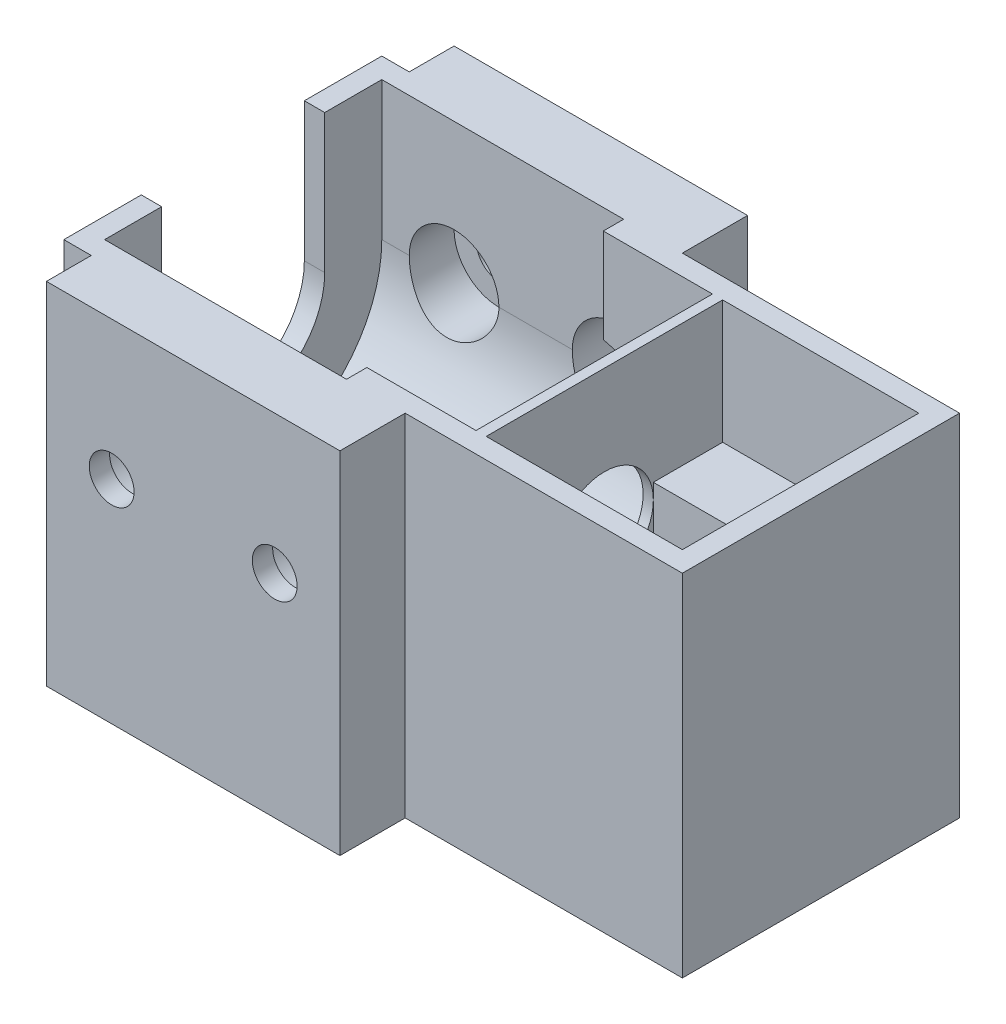
SolidWorks part; units mm, degrees
ref_plane "Front Plane" through (0, 0, 0) normal (0, 0, 1) x (1, 0, 0)
ref_plane "Top Plane" through (0, 0, 0) normal (0, 1, 0) x (1, 0, 0)
ref_plane "Right Plane" through (0, 0, 0) normal (1, 0, 0) x (0, 0, -1)
sketch "Sketch1" plane through (0, 0, 0) normal (0, 0, 1) x (1, 0, 0)
  line L1 (-76.2, -50.8) -> (40.64, -50.8)
  line L2 (-76.2, -50.8) -> (-76.2, 0)
  line L3 (-76.2, 0) -> (40.64, 0)
  line L4 (40.64, -50.8) -> (40.64, 0)
  line L5 (-76.2, -50.8) -> (40.64, 0) construction
  line L6 (-76.2, 0) -> (40.64, -50.8) construction
  point P0 (0, 0)
  dimension "D1" = 116.84
  dimension "D2" = 50.8
  dimension "D3" = 76.2
extrude "Boss-Extrude1" add sketch "Sketch1" along normal mid plane 63.5
sketch "Sketch2" plane through (0, 0, 0) normal (0, 0, 1) x (1, 0, 0)
  line L0 (-152.4829, -25.4) -> (6, -25.4) construction
  line L1 (-49.3609, -3.81) -> (-49.3609, -12.7)
  line L2 (40.64, 0) -> (-76.2, 0) construction
  line L3 (40.64, 0) -> (-76.2, 0) construction
  line L4 (-11.68, -3.81) -> (-11.68, -6.985)
  line L5 (-11.68, -25.4) -> (-11.68, -3.81) construction
  line L6 (-128.4172, -25.4) -> (-157.8092, -25.4)
  line L7 (6, -25.4) -> (40.64, -25.4)
  line L8 (-607.3619, -25.4) -> (6, -25.4) construction
  line L9 (-49.3609, -3.81) -> (-11.68, -3.81)
  line L10 (6, -25.4) -> (-128.4172, -25.4)
  line L11 (-11.68, -6.985) -> (5.32, -6.985)
  line L12 (5.32, -6.985) -> (5.32, -17.78)
  line L13 (5.32, -17.78) -> (23.32, -17.78)
  line L14 (-49.3609, -12.7) -> (-220.2024, -12.7)
  line L15 (-220.2024, -12.7) -> (-220.2024, -25.4)
  line L16 (-220.2024, -25.4) -> (-157.8092, -25.4)
  line L17 (23.32, -17.78) -> (23.32, -25.4) construction
  line L18 (23.32, -17.78) -> (40.64, -17.78)
  line L19 (40.64, -50.8) -> (40.64, 0) construction
  line L20 (40.64, -17.78) -> (40.64, -25.4)
  line L21 (-76.2, 0) -> (-76.2, -50.8) construction
  point P23 (-11.68, -25.4)
  dimension "D1" = 21.59
  dimension "D2" = 37.6809
  dimension "D3" = 25.4
  dimension "D4" = 35
  dimension "D5" = 7.62
  dimension "D6" = 3.175
  dimension "D7" = 26.8391
  dimension "D8" = 18
  dimension "D9" = 12.7
revolve "Cut-Revolve1" cut sketch "Sketch2" angle 360 about L0
sketch "Sketch38" plane through (40.64, 0, 0) normal (1, 0, 0) x (0, 0, -1)
  line L1 (-10, -35.4) -> (10, -35.4)
  line L2 (-10, -35.4) -> (-10, -15.4)
  line L3 (-10, -15.4) -> (10, -15.4)
  line L4 (10, -35.4) -> (10, -15.4)
  line L5 (-10, -35.4) -> (10, -15.4) construction
  line L6 (-10, -15.4) -> (10, -35.4) construction
  point P0 (0, -25.4)
  point P1 (0, -25.4)
  dimension "D1" = 20
  dimension "D2" = 20
extrude "Cut-Extrude33" cut sketch "Sketch38" against normal offset from surface (33.7325 mm away) 1.5875 up to face at (5.32, -43.815, 0)
sketch "Sketch37" plane through (40.64, 0, 0) normal (1, 0, 0) x (0, 0, -1)
  line L0 (31.75, -50.8) -> (31.75, 0) construction
  line L1 (-31.75, 0) -> (31.75, 0)
  line L2 (-31.75, 0) -> (-31.75, -25.4)
  line L3 (-31.75, -25.4) -> (31.75, -25.4)
  line L4 (31.75, 0) -> (31.75, -25.4)
  line L5 (10, -35.4) -> (10, -15.4) construction
  point P7 (0, -25.4)
  point P11 (0, 0)
  point P14 (10, -25.4)
extrude "Cut-Extrude32" cut sketch "Sketch37" against normal through all
sketch "Sketch39" plane through (0, -25.4, 0) normal (0, 1, 0) x (1, 0, 0)
  line L10 (-76.2, 12.7) -> (-49.3609, 12.7)
  line L11 (-49.3609, 12.7) -> (-49.3609, 21.59)
  line L12 (-49.3609, 21.59) -> (-11.68, 21.59)
  line L13 (-11.68, 21.59) -> (-11.68, 18.415)
  line L14 (-11.68, 18.415) -> (5.32, 18.415)
  line L15 (5.32, 18.415) -> (5.32, 7.62)
  line L16 (5.32, 18.415) -> (5.32, 7.62)
  line L17 (40.64, 10) -> (40.64, 31.75)
  line L18 (40.64, 31.75) -> (-76.2, 31.75)
  line L19 (-76.2, 31.75) -> (-76.2, 12.7)
  line L20 (-76.2, 12.7) -> (-49.3609, 12.7)
  line L21 (-49.3609, 12.7) -> (-49.3609, 21.59)
  line L22 (-49.3609, 21.59) -> (-11.68, 21.59)
  line L23 (-11.68, 21.59) -> (-11.68, 18.415)
  line L24 (-11.68, 18.415) -> (5.32, 18.415)
  line L25 (6.9075, 10) -> (40.64, 10)
  line L26 (6.9075, 10) -> (40.64, 10)
  line L27 (40.64, 10) -> (40.64, 31.75)
  line L28 (40.64, 31.75) -> (-76.2, 31.75)
  line L29 (-76.2, 31.75) -> (-76.2, 12.7)
  line L30 (-49.3609, -12.7) -> (-76.2, -12.7)
  line L31 (-76.2, -12.7) -> (-76.2, -31.75)
  line L32 (-76.2, -31.75) -> (40.64, -31.75)
  line L33 (40.64, -31.75) -> (40.64, -10)
  line L34 (40.64, -10) -> (6.9075, -10)
  line L35 (40.64, -10) -> (6.9075, -10)
  line L36 (5.32, -18.415) -> (-11.68, -18.415)
  line L37 (-11.68, -18.415) -> (-11.68, -21.59)
  line L38 (-11.68, -21.59) -> (-49.3609, -21.59)
  line L39 (-49.3609, -21.59) -> (-49.3609, -12.7)
  line L40 (-49.3609, -12.7) -> (-76.2, -12.7)
  line L41 (-76.2, -12.7) -> (-76.2, -31.75)
  line L42 (-76.2, -31.75) -> (40.64, -31.75)
  line L43 (40.64, -31.75) -> (40.64, -10)
  line L44 (5.32, -7.62) -> (5.32, -18.415)
  line L45 (5.32, -7.62) -> (5.32, -18.415)
  line L46 (5.32, -18.415) -> (-11.68, -18.415)
  line L47 (-11.68, -18.415) -> (-11.68, -21.59)
  line L48 (-11.68, -21.59) -> (-49.3609, -21.59)
  line L49 (-49.3609, -21.59) -> (-49.3609, -12.7)
  line L52 (5.32, 7.62) -> (6.9075, 7.62)
  line L53 (5.32, 7.62) -> (6.9075, 7.62)
  line L54 (6.9075, 7.62) -> (6.9075, 10)
  line L55 (6.9075, 7.62) -> (6.9075, 10)
  line L56 (6.9075, -10) -> (6.9075, -7.62)
  line L57 (6.9075, -10) -> (6.9075, -7.62)
  line L58 (6.9075, -7.62) -> (5.32, -7.62)
  line L59 (6.9075, -7.62) -> (5.32, -7.62)
  dimension "D1" = 0
  dimension "D2" = 0
extrude "Boss-Extrude5" add sketch "Sketch39" along normal blind 25.4
sketch "Sketch40" plane through (0, 0, 0) normal (0, 1, 0) x (1, 0, 0)
  line L0 (6.9075, 10) -> (40.64, 10) construction
  line L1 (23.32, 10) -> (40.64, 10)
  line L2 (23.32, 10) -> (23.32, -10)
  line L3 (23.32, -10) -> (40.64, -10)
  line L4 (40.64, 10) -> (40.64, -10)
  line L6 (-11.68, 21.59) -> (-11.68, 18.415) construction
  dimension "D1" = 35
extrude "Boss-Extrude6" add sketch "Sketch40" against normal up to next
sketch "Sketch41" plane through (0, 0, 0) normal (0, 1, 0) x (1, 0, 0)
  line L2 (-76.2, 12.7) -> (-76.2, -12.7) construction
  circle A0 centre (-57.15, 0) radius 3.1134
  circle A1 centre (-31.75, 0) radius 3.1134
  circle A2 centre (-6.35, 0) radius 3.1134
  dimension "D1" = 19.05
extrude "Cut-Extrude34" cut sketch "Sketch41" against normal through all
ref_plane "Plane_Mid" through (0, -25.4, 0) normal (0, 1, 0) x (1, 0, 0)
ref_axis "Axis1" through (6.9075, -25.4, 0) along (-1, 0, 0)
sketch "Sketch42" plane through (0, 0, 0) normal (0, 0, 1) x (1, 0, 0)
  line L0 (1.7462, -25.4) -> (-1.7462, -25.4) construction
  line L1 (-76.2, 0) -> (-76.2, -25.4) construction
  circle A0 centre (-38.1, -25.4) radius 3.4925
  circle A1 centre (-12.7, -25.4) radius 3.4925
  dimension "D1" = 6.985
  dimension "D2" = 38.1
extrude "Cut-Extrude35" cut sketch "Sketch42" against normal through all both and the other way through all
sketch "Sketch43" plane through (0, 0, 0) normal (0, 0, 1) x (1, 0, 0)
  circle A0 centre (-38.1, -25.4) radius 6.985
  circle A1 centre (-12.7, -25.4) radius 6.985
  dimension "D1" = 13.97
extrude "Cut-Extrude36" cut sketch "Sketch43" against normal offset from surface (28.575 mm away) 3.175 up to face at (-9.2075, -25.4, -31.75)
extrude "Cut-Extrude37" cut sketch "Sketch43<2>" along normal offset from surface (28.575 mm away) 3.175 up to face at (-9.2075, -25.4, 31.75)
sketch "Sketch43<2>" plane through (0, 0, 0) normal (0, 0, 1) x (1, 0, 0) same geometry as "Sketch43"
sketch "Sketch44" plane through (0, 0, 0) normal (0, 1, 0) x (1, 0, 0)
  line L0 (5.32, -18.415) -> (-11.68, -18.415) construction
  line L1 (6.9075, 18.415) -> (22.82, 18.415)
  line L2 (6.9075, 18.415) -> (6.9075, -18.415)
  line L3 (6.9075, -18.415) -> (22.82, -18.415)
  line L4 (22.82, 18.415) -> (22.82, -18.415)
  line L5 (-11.68, 18.415) -> (5.32, 18.415) construction
  line L6 (6.9075, 7.62) -> (6.9075, 10) construction
  line L7 (23.32, 10) -> (23.32, -10) construction
  dimension "D1" = 0.5
extrude "Cut-Extrude38" cut sketch "Sketch44" against normal up to surface (35.4 mm away) up to face at (15.1138, -35.4, 0)
sketch "Sketch45" plane through (0, 0, 0) normal (0, 0, 1) x (1, 0, 0)
  line L0 (40.64, 0) -> (-76.2, 0) construction
  line L2 (37.465, 0) -> (22.82, 0)
  line L4 (37.465, 0) -> (37.465, -15.4)
  line L5 (37.465, -15.4) -> (22.82, -15.4)
  line L8 (22.82, 0) -> (22.82, -15.4)
  line L9 (40.64, -50.8) -> (40.64, 0) construction
  line L10 (22.82, -35.4) -> (22.82, 0) construction
  line L11 (-5.715, -25.4) -> (5.32, -25.4) construction
  dimension "D1" = 3.175
  dimension "D2" = 10
extrude "Cut-Extrude39" cut sketch "Sketch45" against normal up to surface and the other way up to surface up to face at (14.8637, -17.7, -18.415) other way up to face at (14.8638, -17.7, 18.415)
sketch "Sketch46" plane through (0, 0, 0) normal (0, 1, 0) x (1, 0, 0)
  line L0 (-11.68, 18.415) -> (5.32, 18.415) construction
  line L1 (40.64, 31.75) -> (-2.54, 31.75)
  line L2 (40.64, 31.75) -> (40.64, 21.59)
  line L3 (40.64, 21.59) -> (-2.54, 21.59)
  line L4 (-2.54, 31.75) -> (-2.54, 21.59)
  line L5 (-76.2, 0) -> (40.64, 0) construction
  line L6 (-76.2, 12.7) -> (-76.2, -12.7) construction
  line L7 (40.64, -31.75) -> (40.64, 31.75) construction
  line L8 (40.64, -31.75) -> (40.64, -21.59)
  line L9 (40.64, -21.59) -> (-2.54, -21.59)
  line L10 (40.64, -31.75) -> (-2.54, -31.75)
  line L11 (-2.54, -31.75) -> (-2.54, -21.59)
  line L12 (-49.3609, 21.59) -> (-11.68, 21.59) construction
  line L13 (-76.2, 31.75) -> (-48.26, 31.75)
  line L14 (-76.2, 31.75) -> (-76.2, 24.765)
  line L15 (-76.2, 24.765) -> (-48.26, 24.765)
  line L16 (-48.26, 31.75) -> (-48.26, 24.765)
  line L17 (-48.26, -31.75) -> (-48.26, -24.765)
  line L18 (-76.2, -24.765) -> (-48.26, -24.765)
  line L19 (-76.2, -31.75) -> (-76.2, -24.765)
  line L20 (-76.2, -31.75) -> (-48.26, -31.75)
  dimension "D1" = 3.175
  dimension "D2" = 3.175
  dimension "D3" = 3.175
  dimension "D4" = 3.175
extrude "Cut-Extrude40" cut sketch "Sketch46" against normal through all
sketch "Sketch49" plane through (0, 0, 0) normal (0, 1, 0) x (1, 0, 0)
  line L0 (-48.26, -24.765) -> (-76.2, -24.765) construction
  line L1 (-76.2, 24.765) -> (-52.5359, 24.765)
  line L2 (-76.2, 24.765) -> (-76.2, -24.765)
  line L3 (-76.2, -24.765) -> (-52.5359, -24.765)
  line L4 (-52.5359, 24.765) -> (-52.5359, -24.765)
  line L5 (-49.3609, -21.59) -> (-49.3609, 21.59) construction
  dimension "D1" = 3.175
extrude "Cut-Extrude42" cut sketch "Sketch49" against normal through all
sketch "Sketch50" plane through (0, 0, 0) normal (0, 1, 0) x (1, 0, 0)
  line L0 (-2.54, 21.59) -> (40.64, 21.59) construction
  line L1 (22.566, 20.066) -> (22.82, 20.066)
  line L2 (22.566, 20.066) -> (22.566, 21.59)
  line L3 (22.566, 21.59) -> (22.82, 21.59)
  line L4 (22.82, 20.066) -> (22.82, 21.59)
  line L5 (22.693, 21.59) -> (22.693, 20.066) construction
  line L6 (22.566, 20.828) -> (22.82, 20.828) construction
  line L8 (22.82, 10) -> (22.82, 18.415) construction
  line L9 (21.042, 20.066) -> (21.296, 20.066)
  line L10 (21.296, 20.066) -> (21.296, 21.59)
  line L11 (21.042, 21.59) -> (21.296, 21.59)
  line L12 (21.042, 20.066) -> (21.042, 21.59)
  line L13 (19.518, 20.066) -> (19.772, 20.066)
  line L14 (19.772, 20.066) -> (19.772, 21.59)
  line L15 (19.518, 21.59) -> (19.772, 21.59)
  line L16 (19.518, 20.066) -> (19.518, 21.59)
  line L17 (17.994, 20.066) -> (18.248, 20.066)
  line L18 (18.248, 20.066) -> (18.248, 21.59)
  line L19 (17.994, 21.59) -> (18.248, 21.59)
  line L20 (17.994, 20.066) -> (17.994, 21.59)
  line L21 (16.47, 20.066) -> (16.724, 20.066)
  line L22 (16.724, 20.066) -> (16.724, 21.59)
  line L23 (16.47, 21.59) -> (16.724, 21.59)
  line L24 (16.47, 20.066) -> (16.47, 21.59)
  line L25 (14.946, 20.066) -> (15.2, 20.066)
  line L26 (15.2, 20.066) -> (15.2, 21.59)
  line L27 (14.946, 21.59) -> (15.2, 21.59)
  line L28 (14.946, 20.066) -> (14.946, 21.59)
  line L29 (13.422, 20.066) -> (13.676, 20.066)
  line L30 (13.676, 20.066) -> (13.676, 21.59)
  line L31 (13.422, 21.59) -> (13.676, 21.59)
  line L32 (13.422, 20.066) -> (13.422, 21.59)
  line L33 (11.898, 20.066) -> (12.152, 20.066)
  line L34 (12.152, 20.066) -> (12.152, 21.59)
  line L35 (11.898, 21.59) -> (12.152, 21.59)
  line L36 (11.898, 20.066) -> (11.898, 21.59)
  line L37 (10.374, 20.066) -> (10.628, 20.066)
  line L38 (10.628, 20.066) -> (10.628, 21.59)
  line L39 (10.374, 21.59) -> (10.628, 21.59)
  line L40 (10.374, 20.066) -> (10.374, 21.59)
  line L41 (8.85, 20.066) -> (9.104, 20.066)
  line L42 (9.104, 20.066) -> (9.104, 21.59)
  line L43 (8.85, 21.59) -> (9.104, 21.59)
  line L44 (8.85, 20.066) -> (8.85, 21.59)
  point P0 (22.693, 20.828)
  dimension "D1" = 0.254
  dimension "D2" = 1.524
  dimension "D3" = 10
extrude "Cut-Extrude43" cut sketch "Sketch50" against normal blind 2.54
sketch "Sketch52" plane through (23.32, 0, 0) normal (-1, 0, 0) x (0, 0, 1)
  circle A0 centre (0, -25.4) radius 0.3175
  dimension "D1" = 0.635
extrude "Cut-Extrude45" cut sketch "Sketch52" against normal blind 0.0508
sketch "Sketch53" plane through (23.32, 0, 0) normal (-1, 0, 0) x (0, 0, 1)
  circle A0 centre (0, -25.4) radius 2
  dimension "D1" = 4
extrude "Cut-Extrude46" cut sketch "Sketch53" against normal blind 0.0254
sketch "Sketch54" plane through (0, -35.4, 0) normal (0, 1, 0) x (1, 0, 0)
  line L0 (22.82, 10) -> (22.82, -10)
  line L8 (23.32, 10) -> (22.82, 10)
  line L9 (22.82, 10) -> (22.82, 18.415)
  line L10 (22.82, 18.415) -> (6.9075, 18.415)
  line L11 (6.9075, 18.415) -> (6.9075, -18.415)
  line L12 (6.9075, -18.415) -> (22.82, -18.415)
  line L13 (22.82, -18.415) -> (22.82, -10)
  line L14 (22.82, -10) -> (23.32, -10)
  line L15 (23.32, -10) -> (23.32, 10)
  line L17 (22.82, 10) -> (22.82, 18.415)
  line L18 (22.82, 18.415) -> (6.9075, 18.415)
  line L19 (6.9075, 18.415) -> (6.9075, -18.415)
  line L20 (6.9075, -18.415) -> (22.82, -18.415)
  line L21 (22.82, -18.415) -> (22.82, -10)
  dimension "D1" = 0
extrude "Boss-Extrude7" add sketch "Sketch54" along normal blind 2.54
sketch "Sketch55" plane through (0, -32.86, 0) normal (0, 1, 0) x (1, 0, 0)
  line L0 (22.82, -18.415) -> (22.82, -10) construction
  line L1 (22.82, 10) -> (6.9075, 10)
  line L2 (22.82, 10) -> (22.82, 18.415)
  line L3 (22.82, 18.415) -> (6.9075, 18.415)
  line L4 (6.9075, 10) -> (6.9075, 18.415)
  line L5 (22.82, 10) -> (6.9075, 18.415) construction
  line L6 (22.82, 18.415) -> (6.9075, 10) construction
  line L7 (6.9075, -18.415) -> (22.82, -18.415)
  line L8 (6.9075, -18.415) -> (6.9075, -10)
  line L9 (6.9075, -10) -> (22.82, -10)
  line L10 (22.82, -18.415) -> (22.82, -10)
  line L11 (6.9075, -18.415) -> (22.82, -10) construction
  line L12 (6.9075, -10) -> (22.82, -18.415) construction
  point P4 (14.8637, 14.2075)
  point P5 (0, 0)
  point P11 (14.8637, -14.2075)
  point P15 (0, 0)
  point P17 (0, 0)
extrude "Boss-Extrude8" add sketch "Sketch55" along normal up to surface (17.46 mm away) up to face at (26.6063, -15.4, 0)
sketch "Sketch56" plane through (0, 0, 0) normal (0, 0, 1) x (1, 0, 0)
  line L0 (16.47, -27.4) -> (16.47, -32.86) construction
  line L1 (23.3454, -27.4) -> (16.47, -27.4) construction
  line L2 (23.3454, -23.4) -> (23.3454, -27.4) construction
  line L3 (6.9075, -25.4) -> (5.32, -25.4) construction
  line L4 (6.9075, -32.86) -> (6.9075, -25.4) construction
  line L5 (11.6888, -30.13) -> (6.9075, -30.13) construction
  line L6 (11.6888, -30.13) -> (16.47, -30.13) construction
  line L7 (16.47, -27.4) -> (22.82, -27.4)
  line L8 (22.82, -27.4) -> (22.82, -32.86)
  line L9 (6.9075, -32.86) -> (22.82, -32.86)
  spline S0 degree 3 poles (6.9075, -32.86) (7.8397, -32.86) (14.8054, -27.986) (15.1522, -27.4) (16.47, -27.4) knots 0 0 0 0 0.327131 1 1 1 1
  point P6 (16.47, -30.13)
  point P8 (0, 0)
  point P11 (6.9075, -32.86)
  dimension "D1" = 2
  dimension "D2" = 6.35
extrude "Boss-Extrude9" add sketch "Sketch56" along normal up to next and the other way up to next
sketch "Sketch57" plane through (0, -15.4, 0) normal (0, 1, 0) x (1, 0, 0)
  line L8 (23.32, -10) -> (6.9075, -10)
  line L9 (6.9075, -10) -> (6.9075, -18.415)
  line L10 (6.9075, -18.415) -> (37.465, -18.415)
  line L11 (37.465, -18.415) -> (37.465, 18.415)
  line L12 (37.465, 18.415) -> (6.9075, 18.415)
  line L13 (23.32, -10) -> (6.9075, -10)
  line L14 (6.9075, 18.415) -> (6.9075, 10)
  line L15 (23.32, 10) -> (23.32, -10)
  line L16 (6.9075, 18.415) -> (6.9075, 10)
  line L17 (6.9075, -10) -> (6.9075, -18.415)
  line L18 (6.9075, -18.415) -> (37.465, -18.415)
  line L19 (37.465, -18.415) -> (37.465, 18.415)
  line L20 (37.465, 18.415) -> (6.9075, 18.415)
  line L21 (6.9075, 10) -> (23.32, 10)
  line L22 (6.9075, 10) -> (23.32, 10)
  line L23 (23.32, 10) -> (23.32, -10)
  dimension "D1" = 0
extrude "Cut-Extrude47" cut sketch "Sketch57" against normal blind 7.62
sketch "Sketch58" plane through (0, -50.8, 0) normal (0, -1, 0) x (1, 0, 0)
  line L12 (-48.26, 24.765) -> (-52.5359, 24.765)
  line L13 (-52.5359, 24.765) -> (-52.5359, -24.765)
  line L14 (-52.5359, -24.765) -> (-48.26, -24.765)
  line L15 (-48.26, -24.765) -> (-48.26, -31.75)
  line L16 (-48.26, -31.75) -> (-2.54, -31.75)
  line L17 (-2.54, -31.75) -> (-2.54, -21.59)
  line L18 (-2.54, -21.59) -> (40.64, -21.59)
  line L19 (40.64, -21.59) -> (40.64, 21.59)
  line L20 (40.64, 21.59) -> (-2.54, 21.59)
  line L21 (-2.54, 21.59) -> (-2.54, 31.75)
  line L22 (-2.54, 31.75) -> (-48.26, 31.75)
  line L23 (-48.26, 31.75) -> (-48.26, 24.765)
  line L24 (-48.26, 24.765) -> (-52.5359, 24.765)
  line L25 (-52.5359, 24.765) -> (-52.5359, -24.765)
  line L26 (-52.5359, -24.765) -> (-48.26, -24.765)
  line L27 (-48.26, -24.765) -> (-48.26, -31.75)
  line L28 (-48.26, -31.75) -> (-2.54, -31.75)
  line L29 (-2.54, -31.75) -> (-2.54, -21.59)
  line L30 (-2.54, -21.59) -> (40.64, -21.59)
  line L31 (40.64, -21.59) -> (40.64, 21.59)
  line L32 (40.64, 21.59) -> (-2.54, 21.59)
  line L33 (-2.54, 21.59) -> (-2.54, 31.75)
  line L34 (-2.54, 31.75) -> (-48.26, 31.75)
  line L35 (-48.26, 31.75) -> (-48.26, 24.765)
  circle A0 centre (-31.75, 0) radius 3.1134
  circle A1 centre (-6.35, 0) radius 3.1134
  circle A2 centre (-6.35, 0) radius 3.1134 construction
  circle A3 centre (-31.75, 0) radius 3.1134 construction
  dimension "D1" = 0
extrude "Boss-Extrude10" add sketch "Sketch58" along normal blind 7.62
sketch "Sketch59" plane through (0, -35.4, 0) normal (0, 1, 0) x (1, 0, 0)
  line L4 (22.82, 10) -> (22.82, -10)
  line L5 (22.82, -10) -> (23.32, -10)
  line L6 (23.32, -10) -> (23.32, 10)
  line L7 (23.32, 10) -> (22.82, 10)
  line L8 (22.82, 10) -> (22.82, -10)
  line L9 (22.82, -10) -> (23.32, -10)
  line L10 (23.32, -10) -> (23.32, 10)
  line L11 (23.32, 10) -> (22.82, 10)
  dimension "D1" = 0
extrude "Cut-Extrude48" cut sketch "Sketch59" against normal blind 7.62
sketch "Sketch51" plane through (0, -23.02, 0) normal (0, 1, 0) x (1, 0, 0)
  line L0 (24.844, 0.127) -> (26.1082, 0.127)
  line L1 (24.59, 1.27) -> (24.844, 1.27)
  line L2 (24.59, 1.27) -> (24.59, 0.127)
  line L3 (24.59, -1.27) -> (24.844, -1.27)
  line L4 (24.844, 1.27) -> (24.844, 0.127)
  line L5 (29.3987, -0.127) -> (30.6629, -0.127)
  line L6 (24.844, -0.127) -> (24.844, -1.27)
  line L7 (26.3622, 1.27) -> (26.3622, 0.127)
  line L8 (26.1082, 1.27) -> (26.3622, 1.27)
  line L9 (26.1082, 1.27) -> (26.1082, 0.127)
  line L10 (26.1082, -1.27) -> (26.3622, -1.27)
  line L11 (27.8804, 1.27) -> (27.8804, 0.127)
  line L12 (27.6264, 1.27) -> (27.8804, 1.27)
  line L13 (27.6264, 1.27) -> (27.6264, 0.127)
  line L14 (27.6264, -1.27) -> (27.8804, -1.27)
  line L15 (29.3987, 1.27) -> (29.3987, 0.127)
  line L16 (29.1447, 1.27) -> (29.3987, 1.27)
  line L17 (29.1447, 1.27) -> (29.1447, 0.127)
  line L18 (29.1447, -1.27) -> (29.3987, -1.27)
  line L19 (30.9169, 1.27) -> (30.9169, 0.127)
  line L20 (30.6629, 1.27) -> (30.9169, 1.27)
  line L21 (30.6629, 1.27) -> (30.6629, 0.127)
  line L22 (30.6629, -1.27) -> (30.9169, -1.27)
  line L23 (32.4351, 1.27) -> (32.4351, 0.127)
  line L24 (32.1811, 1.27) -> (32.4351, 1.27)
  line L25 (32.1811, 1.27) -> (32.1811, 0.127)
  line L26 (32.1811, -1.27) -> (32.4351, -1.27)
  line L27 (33.9533, 1.27) -> (33.9533, 0.127)
  line L28 (33.6993, 1.27) -> (33.9533, 1.27)
  line L29 (33.6993, 1.27) -> (33.6993, 0.127)
  line L30 (33.6993, -1.27) -> (33.9533, -1.27)
  line L31 (35.4715, 1.27) -> (35.4715, 0.127)
  line L32 (35.2175, 1.27) -> (35.4715, 1.27)
  line L33 (35.2175, 1.27) -> (35.2175, 0.127)
  line L34 (35.2175, -1.27) -> (35.4715, -1.27)
  line L35 (35.258, 2.5876) -> (24.1619, 2.5876) construction
  line L36 (23.32, 11.7754) -> (37.465, 11.7754) construction
  line L37 (24.844, -0.127) -> (26.1082, -0.127)
  line L38 (23.32, 10) -> (23.32, -10) construction
  line L39 (37.465, -18.415) -> (37.465, 18.415) construction
  line L40 (23.32, 0.127) -> (24.59, 0.127)
  line L41 (23.32, 0.127) -> (23.32, -0.127)
  line L42 (23.32, -0.127) -> (24.59, -0.127)
  line L43 (37.465, 0.127) -> (37.465, -0.127)
  line L44 (30.9169, 0.127) -> (32.1811, 0.127)
  line L46 (24.59, -0.127) -> (24.59, -1.27)
  line L47 (26.1082, -0.127) -> (26.1082, -1.27)
  line L48 (26.3622, 0.127) -> (27.6264, 0.127)
  line L49 (26.3622, -0.127) -> (26.3622, -1.27)
  line L51 (26.3622, -0.127) -> (27.6264, -0.127)
  line L52 (27.6264, -0.127) -> (27.6264, -1.27)
  line L53 (27.8804, 0.127) -> (29.1447, 0.127)
  line L54 (27.8804, -0.127) -> (29.1447, -0.127)
  line L55 (27.8804, -0.127) -> (27.8804, -1.27)
  line L56 (29.1447, -0.127) -> (29.1447, -1.27)
  line L57 (29.3987, 0.127) -> (30.6629, 0.127)
  line L58 (30.9169, -0.127) -> (32.1811, -0.127)
  line L61 (29.3987, -0.127) -> (29.3987, -1.27)
  line L62 (30.6629, -0.127) -> (30.6629, -1.27)
  line L63 (30.9169, -0.127) -> (30.9169, -1.27)
  line L64 (32.1811, -0.127) -> (32.1811, -1.27)
  line L65 (32.4351, 0.127) -> (33.6993, 0.127)
  line L66 (32.4351, -0.127) -> (33.6993, -0.127)
  line L67 (32.4351, -0.127) -> (32.4351, -1.27)
  line L68 (33.6993, -0.127) -> (33.6993, -1.27)
  line L69 (33.9533, 0.127) -> (35.2175, 0.127)
  line L70 (33.9533, -0.127) -> (35.2175, -0.127)
  line L71 (33.9533, -0.127) -> (33.9533, -1.27)
  line L72 (35.2175, -0.127) -> (35.2175, -1.27)
  line L73 (35.4715, -0.127) -> (35.4715, -1.27)
  line L74 (35.4715, 0.127) -> (37.465, 0.127)
  line L75 (35.4715, -0.127) -> (37.465, -0.127)
  text T0 "<b>494 kHz WL/2</b>" font "Century Gothic" height 1.27
  text T1 "<b>v6</b>"
  point P0 (24.717, 0)
  point P51 (30.3925, 0)
  point P52 (23.32, 0)
  dimension "D1" = 0.254
  dimension "D2" = 2.54
  dimension "D3" = 1.5182
  dimension "D5" = 0.8419
  dimension "D6" = 0.254
  dimension "D4" = 8
extrude "Cut-Extrude44" cut sketch "Sketch51" against normal blind 0.635
sketch "Sketch60" plane through (0, 0, 0) normal (0, 1, 0) x (1, 0, 0)
  line L1 (-60.6783, -40.5295) -> (60.6783, -40.5295)
  line L2 (-60.6783, -40.5295) -> (-60.6783, 40.5295)
  line L3 (-60.6783, 40.5295) -> (60.6783, 40.5295)
  line L4 (60.6783, -40.5295) -> (60.6783, 40.5295)
  line L5 (0, 40.5295) -> (0, -40.5295) construction
  line L6 (-60.6783, 0) -> (60.6783, 0) construction
  point P0 (0, 0)
extrude "Cut-Extrude49" cut sketch "Sketch60" against normal blind 10.16
ref_plane "Plane_Bottom" through (0, -46.99, 0) normal (0, 1, 0) x (1, 0, 0)
ref_plane "Plane_Top" through (0, -3.81, 0) normal (0, 1, 0) x (1, 0, 0)
sketch "Sketch61" plane through (5.32, 0, 0) normal (-1, 0, 0) x (0, 0, 1)
  circle A0 centre (0, -25.4) radius 7.62
  circle A1 centre (0, -25.4) radius 8.9762
extrude "Boss-Extrude11" add sketch "Sketch61" against normal up to surface (1.5875 mm away) up to face at (6.9075, -21.9643, -11.5543)
sketch "Sketch62" plane through (0, -10.16, 0) normal (0, 1, 0) x (1, 0, 0)
  line L1 (6.9075, 7.62) -> (5.32, 7.62)
  line L2 (6.9075, 7.62) -> (6.9075, -7.62)
  line L3 (6.9075, -7.62) -> (5.32, -7.62)
  line L4 (5.32, 7.62) -> (5.32, -7.62)
  line L5 (6.9075, 7.62) -> (5.32, -7.62) construction
  line L6 (6.9075, -7.62) -> (5.32, 7.62) construction
  point P4 (6.1137, 0)
extrude "Boss-Extrude12" add sketch "Sketch62" against normal up to next
sketch "Sketch64" plane through (0, -10.16, 0) normal (0, 1, 0) x (1, 0, 0)
  line L25 (37.465, 18.415) -> (6.9075, 18.415)
  line L26 (37.465, 18.415) -> (37.465, -18.415)
  line L27 (37.465, -18.415) -> (6.9075, -18.415)
  line L28 (6.9075, 18.415) -> (6.9075, -18.415)
  line L29 (37.465, 18.415) -> (6.9075, -18.415) construction
  line L30 (37.465, -18.415) -> (6.9075, 18.415) construction
  line L48 (-11.68, 18.415) -> (5.32, 18.415)
  line L49 (5.32, 18.415) -> (5.32, -18.415)
  line L50 (5.32, -18.415) -> (-11.68, -18.415)
  line L51 (-11.68, -18.415) -> (-11.68, -21.59)
  line L52 (-11.68, -21.59) -> (-49.3609, -21.59)
  line L53 (-49.3609, -21.59) -> (-49.3609, -12.7)
  line L54 (-49.3609, -12.7) -> (-52.5359, -12.7)
  line L55 (-52.5359, -12.7) -> (-52.5359, -24.765)
  line L56 (-52.5359, -24.765) -> (-48.26, -24.765)
  line L57 (-48.26, -24.765) -> (-48.26, -31.75)
  line L58 (-48.26, -31.75) -> (-2.54, -31.75)
  line L59 (-2.54, -31.75) -> (-2.54, -21.59)
  line L60 (-2.54, -21.59) -> (40.64, -21.59)
  line L61 (40.64, -21.59) -> (40.64, 21.59)
  line L62 (40.64, 21.59) -> (-2.54, 21.59)
  line L63 (-2.54, 21.59) -> (-2.54, 31.75)
  line L64 (-2.54, 31.75) -> (-48.26, 31.75)
  line L65 (-48.26, 31.75) -> (-48.26, 24.765)
  line L66 (-48.26, 24.765) -> (-52.5359, 24.765)
  line L67 (-52.5359, 24.765) -> (-52.5359, 12.7)
  line L68 (-52.5359, 12.7) -> (-49.3609, 12.7)
  line L69 (-49.3609, 12.7) -> (-49.3609, 21.59)
  line L70 (-49.3609, 21.59) -> (-11.68, 21.59)
  line L71 (-11.68, 21.59) -> (-11.68, 18.415)
  line L72 (-11.68, 18.415) -> (5.32, 18.415)
  line L73 (5.32, 18.415) -> (5.32, -18.415)
  line L74 (5.32, -18.415) -> (-11.68, -18.415)
  line L75 (-11.68, -18.415) -> (-11.68, -21.59)
  line L76 (-11.68, -21.59) -> (-49.3609, -21.59)
  line L77 (-49.3609, -21.59) -> (-49.3609, -12.7)
  line L78 (-49.3609, -12.7) -> (-52.5359, -12.7)
  line L79 (-52.5359, -12.7) -> (-52.5359, -24.765)
  line L80 (-52.5359, -24.765) -> (-48.26, -24.765)
  line L81 (-48.26, -24.765) -> (-48.26, -31.75)
  line L82 (-48.26, -31.75) -> (-2.54, -31.75)
  line L83 (-2.54, -31.75) -> (-2.54, -21.59)
  line L84 (-2.54, -21.59) -> (40.64, -21.59)
  line L85 (40.64, -21.59) -> (40.64, 21.59)
  line L86 (40.64, 21.59) -> (-2.54, 21.59)
  line L87 (-2.54, 21.59) -> (-2.54, 31.75)
  line L88 (-2.54, 31.75) -> (-48.26, 31.75)
  line L89 (-48.26, 31.75) -> (-48.26, 24.765)
  line L90 (-48.26, 24.765) -> (-52.5359, 24.765)
  line L91 (-52.5359, 24.765) -> (-52.5359, 12.7)
  line L92 (-52.5359, 12.7) -> (-49.3609, 12.7)
  line L93 (-49.3609, 12.7) -> (-49.3609, 21.59)
  line L94 (-49.3609, 21.59) -> (-11.68, 21.59)
  line L95 (-11.68, 21.59) -> (-11.68, 18.415)
  point P28 (22.1862, 0)
  dimension "D1" = 0
extrude "Boss-Extrude14" add sketch "Sketch64" along normal up to surface (6.35 mm away) up to plane "Plane_Top"
sketch "Sketch65" plane through (6.9075, 0, 0) normal (1, 0, 0) x (0, 0, -1)
  line L0 (-10, -23.02) -> (-7.62, -23.02)
  line L1 (10, -23.02) -> (7.62, -23.02)
  line L2 (-7.62, -32.86) -> (-7.62, -23.02)
  line L3 (7.62, -32.86) -> (7.62, -23.02)
  line L6 (-10, -23.02) -> (-10, -32.86)
  line L7 (-10, -32.86) -> (-7.62, -32.86)
  line L8 (7.62, -32.86) -> (10, -32.86)
  line L28 (10, -32.86) -> (10, -23.02)
  point P1 (0, 0)
  point P3 (0, 0)
  point P4 (0, 0)
  point P12 (8.81, -23.02)
extrude "Boss-Extrude16" add sketch "Sketch65" along normal up to next
sketch "Sketch66" plane through (0, -23.02, 0) normal (0, 1, 0) x (1, 0, 0)
  line L1 (23.32, 10) -> (22.82, 10)
  line L2 (23.32, 10) -> (23.32, -10)
  line L3 (23.32, -10) -> (22.82, -10)
  line L4 (22.82, 10) -> (22.82, -10)
  line L5 (23.32, 10) -> (22.82, -10) construction
  line L6 (23.32, -10) -> (22.82, 10) construction
  line L7 (22.82, 7.62) -> (22.82, -7.62) construction
  line L9 (6.9075, 0) -> (5.32, 0) construction
  line L10 (23.32, -0.127) -> (23.32, -7.62) construction
  point P4 (23.07, 0)
  point P6 (0, 0)
  point P7 (0, 0)
  point P10 (0, 0)
  point P15 (22.685, -3.5933)
  dimension "D1" = 20
extrude "Cut-Extrude50" cut sketch "Sketch66" against normal up to surface (20 mm away) up to face at (23.07, -43.02, 0)
